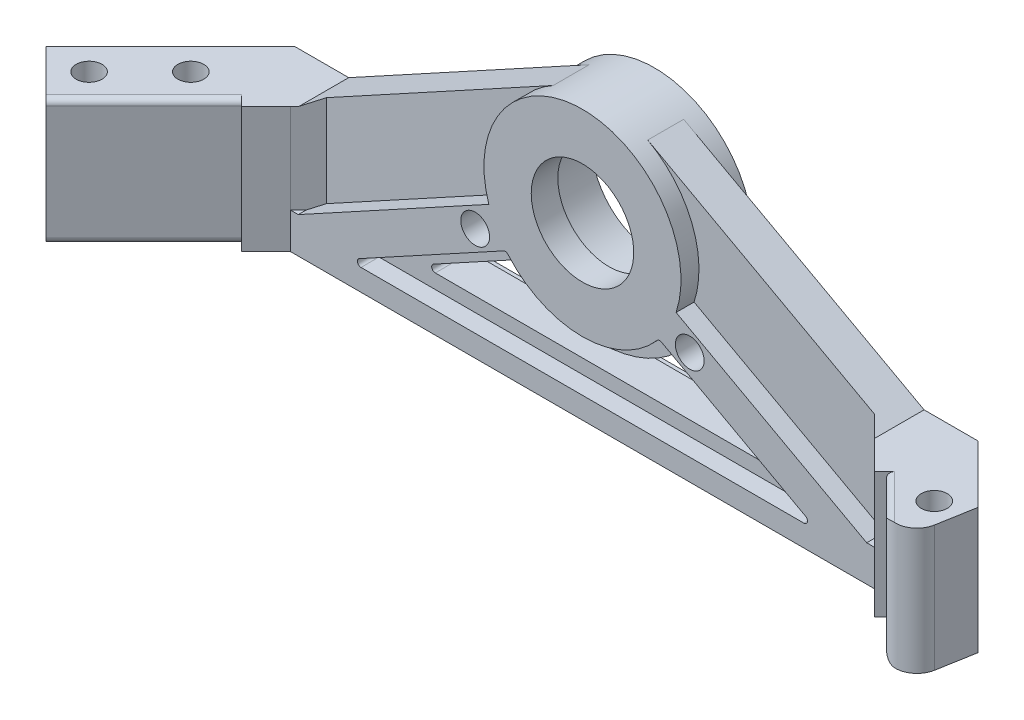
SolidWorks part; units mm, degrees
note: The reader was unsure of these and kept them because the rebuilt part matched: shared geometry of "Sketch2<3>", "Sketch2<5>", "Sketch5<3>".
ref_plane "Front Plane" through (0, 0, 0) normal (0, 0, 1) x (1, 0, 0)
ref_plane "Top Plane" through (0, 0, 0) normal (0, 1, 0) x (1, 0, 0)
ref_plane "Right Plane" through (0, 0, 0) normal (1, 0, 0) x (0, 0, -1)
sketch "Sketch1" plane through (0, 0, 0) normal (0, 1, 0) x (-1, 0, 0)
  line L48 (74.9309, 32.5085) -> (74.2125, 33.2269)
  line L49 (74.2125, 33.2269) -> (56.9345, 15.9489)
  line L50 (57.6529, 15.2305) -> (56.9345, 15.9489)
  line L51 (-56.9345, 15.9489) -> (-74.2125, 33.2269)
  line L52 (-74.2125, 33.2269) -> (-74.9309, 32.5085)
  line L53 (-56.9345, 15.9489) -> (-57.6529, 15.2305)
  line L54 (-65.0167, 7.8667) -> (-61.5144, 4.3644)
  line L55 (-61.5144, 4.3644) -> (-52.3715, 13.5073)
  line L56 (-52.3715, 13.5073) -> (-55.8738, 17.0096)
  line L57 (-55.8738, 17.0096) -> (-65.0167, 7.8667)
  line L58 (55.8738, 17.0096) -> (52.3715, 13.5073)
  line L59 (52.3715, 13.5073) -> (61.5144, 4.3644)
  line L60 (61.5144, 4.3644) -> (65.0167, 7.8667)
  line L61 (65.0167, 7.8667) -> (55.8738, 17.0096)
  line L62 (17.3112, 9.525) -> (13.6482, 9.525)
  line L63 (17.3112, 12.7) -> (-17.3112, 12.7)
  line L64 (-13.6482, 9.525) -> (-17.3112, 9.525)
  line L65 (-17.3112, 3.175) -> (-13.6482, 3.175)
  line L66 (-17.3112, 0) -> (17.3112, 0)
  line L67 (13.6482, 3.175) -> (17.3112, 3.175)
  line L68 (-17.3112, 12.7) -> (-53.1788, 12.7)
  line L69 (-53.1788, 12.7) -> (-50.0038, 9.525)
  line L70 (-50.0038, 9.525) -> (-17.3112, 9.525)
  line L71 (-60.325, 3.175) -> (-57.15, 0)
  line L72 (-57.15, 0) -> (-17.3112, 0)
  line L73 (-17.3112, 3.175) -> (-60.325, 3.175)
  line L74 (17.3112, 9.525) -> (50.0038, 9.525)
  line L75 (50.0038, 9.525) -> (53.1788, 12.7)
  line L76 (53.1788, 12.7) -> (17.3112, 12.7)
  line L77 (57.15, 0) -> (60.325, 3.175)
  line L78 (60.325, 3.175) -> (17.3112, 3.175)
  line L79 (17.3112, 0) -> (57.15, 0)
  line L80 (-74.9309, 32.5085) -> (-82.2947, 25.1447)
  line L81 (-82.2947, 25.1447) -> (-65.0167, 7.8667)
  line L82 (-65.0167, 7.8667) -> (-57.6529, 15.2305)
  line L83 (-60.325, 3.175) -> (-13.6482, 3.175)
  line L84 (-13.6482, 9.525) -> (-50.0038, 9.525)
  line L85 (-50.0038, 9.525) -> (-53.1788, 12.7)
  line L86 (-53.1788, 12.7) -> (-61.5144, 4.3644)
  line L87 (-61.5144, 4.3644) -> (-60.325, 3.175)
  line L88 (13.6482, 3.175) -> (60.325, 3.175)
  line L89 (60.325, 3.175) -> (61.5144, 4.3644)
  line L90 (61.5144, 4.3644) -> (53.1788, 12.7)
  line L91 (53.1788, 12.7) -> (50.0038, 9.525)
  line L92 (50.0038, 9.525) -> (13.6482, 9.525)
  line L93 (82.2947, 25.1447) -> (74.9309, 32.5085)
  line L94 (57.6529, 15.2305) -> (65.0167, 7.8667)
  line L95 (65.0167, 7.8667) -> (82.2947, 25.1447)
sketch "Sketch3" plane through (0, 0, 0) normal (0, 1, 0) x (1, 0, 0)
  line L0 (-53.1788, -12.7) -> (-17.3112, -12.7) construction
  line L1 (-17.3112, 0) -> (-57.15, 0) construction
  line L2 (-57.15, 0) -> (-60.325, -3.175) construction
  line L3 (-60.325, -3.175) -> (-61.5144, -4.3644) construction
  line L4 (-61.5144, -4.3644) -> (-65.0167, -7.8667) construction
  line L5 (-74.2125, -33.2269) -> (-56.9345, -15.9489) construction
  line L6 (-74.9309, -32.5085) -> (-74.2125, -33.2269) construction
  line L7 (-82.2947, -25.1447) -> (-74.9309, -32.5085) construction
  line L8 (-65.0167, -7.8667) -> (-82.2947, -25.1447) construction
  line L9 (-51.5642, -12.7) -> (-17.3112, -12.7)
  line L10 (-17.3112, 0) -> (-57.15, 0)
  line L11 (-57.15, 0) -> (-60.325, -3.175)
  line L12 (-60.325, -3.175) -> (-61.5144, -4.3644)
  line L13 (-61.5144, -4.3644) -> (-65.0167, -7.8667)
  line L14 (-74.2125, -33.2269) -> (-56.9345, -15.9489)
  line L15 (-74.9309, -32.5085) -> (-74.2125, -33.2269)
  line L16 (-82.2947, -25.1447) -> (-74.9309, -32.5085)
  line L17 (-65.0167, -7.8667) -> (-82.2947, -25.1447)
  line L18 (0, 0) -> (0, -12.7) construction
  line L19 (-17.3112, -12.7) -> (17.3112, -12.7) construction
  line L20 (17.3112, 0) -> (-17.3112, 0) construction
  line L21 (-52.3715, -13.5073) -> (-61.5144, -4.3644) construction
  line L22 (-65.0167, -7.8667) -> (-55.8738, -17.0096) construction
  line L23 (-55.8738, -17.0096) -> (-52.3715, -13.5073) construction
  line L24 (17.3112, 0) -> (-17.3112, 0)
  line L25 (-17.3112, -12.7) -> (17.3112, -12.7)
  line L26 (-52.3715, -13.5073) -> (-61.5144, -4.3644)
  line L27 (-65.0167, -7.8667) -> (-55.8738, -17.0096)
  line L28 (-55.8738, -17.0096) -> (-52.3715, -13.5073)
  line L29 (55.8738, -17.0096) -> (52.3715, -13.5073)
  line L30 (65.0167, -7.8667) -> (55.8738, -17.0096)
  line L31 (52.3715, -13.5073) -> (61.5144, -4.3644)
  line L32 (65.0167, -7.8667) -> (82.2947, -25.1447)
  line L33 (82.2947, -25.1447) -> (74.9309, -32.5085)
  line L34 (74.9309, -32.5085) -> (74.2125, -33.2269)
  line L35 (74.2125, -33.2269) -> (56.9345, -15.9489)
  line L36 (61.5144, -4.3644) -> (65.0167, -7.8667)
  line L37 (60.325, -3.175) -> (61.5144, -4.3644)
  line L38 (57.15, 0) -> (60.325, -3.175)
  line L39 (17.3112, 0) -> (57.15, 0)
  line L40 (51.5642, -12.7) -> (17.3112, -12.7)
  line L41 (-52.3715, -13.5073) -> (-51.5642, -12.7)
  line L42 (52.3715, -13.5073) -> (51.5642, -12.7)
extrude "Boss-Extrude1" add sketch "Sketch3" along normal mid plane 22.225 contours L27 L17 L16 L15 L14 | L27 L28 L26 L13 | L18 L24 L10 L11 L12 L26 L41 L9 L25 | L24 L18 L25 L40 L42 L31 L37 L38 L39 | L36 L31 L29 L30 | L35 L34 L33 L32 L30
sketch "Sketch2" plane through (0, 0, 0) normal (0, 0, 1) x (1, 0, 0)
  line L0 (0, 0) -> (0, 36.45) construction
  line L1 (-17.3112, 0) -> (17.3112, 0) construction
  line L2 (50.8048, 11.1125) -> (8.3447, 34.3184)
  line L3 (-50.8048, 11.1125) -> (-8.3447, 34.3184)
  line L4 (50.8048, 11.1125) -> (15.4841, 11.1125)
  line L5 (57.15, 11.1125) -> (-57.15, 11.1125) construction
  line L6 (-50.8048, 11.1125) -> (-15.4841, 11.1125)
  circle A0 centre (0, 19.05) radius 11.05
  circle A1 centre (0, 19.05) radius 17.4
  circle A2 centre (0, 19.05) radius 9.05
  dimension "D1" = 22.1
  dimension "D2" = 6.35
  dimension "D4" = 2
  dimension "D3" = 19.05
extrude "Boss-Extrude2" add sketch "Sketch2" along normal up to surface (12.7 mm away) contours A1 L3 L6 | A1 L0 A0 | A0 L0 | L0 A0 | L0 A1 A0 | A1 L4 L2 | A2
extrude "Cut-Extrude2" cut sketch "Sketch2<3>" along normal blind 8 contours A0 L0 A2 | A2 L0 | L0 A2 | L0 A0 A2
sketch "Sketch2<3>" plane through (0, 0, 0) normal (0, 0, 1) x (1, 0, 0) same geometry as "Sketch2"
extrude "Cut-Extrude3" cut sketch "Sketch2<5>" along normal through all contours A2 L0 | L0 A2
sketch "Sketch2<5>" plane through (0, 0, 0) normal (0, 0, 1) x (1, 0, 0) same geometry as "Sketch2"
sketch "Sketch5" plane through (0, 0, 0) normal (0, 0, -1) x (-1, 0, 0)
  line L0 (-16.5348, 13.6314) -> (-57.15, -8.5663)
  line L1 (-48.5682, -11.1125) -> (-13.4894, 8.0593)
  line L2 (0, 19.05) -> (-55.1885, -11.1125) construction
  line L3 (0, 19.05) -> (0, -11.1125) construction
  line L4 (16.5348, 13.6314) -> (57.15, -8.5663)
  line L5 (48.5682, -11.1125) -> (13.4894, 8.0593)
  line L6 (0, 19.05) -> (55.1885, -11.1125) construction
  line L7 (57.15, 11.1125) -> (50.8048, 11.1125)
  line L8 (50.8048, 11.1125) -> (8.3447, 34.3184)
  line L9 (-8.3447, 34.3184) -> (-50.8048, 11.1125)
  line L10 (-50.8048, 11.1125) -> (-57.15, 11.1125)
  line L11 (-57.15, 11.1125) -> (-57.15, -11.1125)
  line L12 (-57.15, -11.1125) -> (57.15, -11.1125)
  line L13 (57.15, -11.1125) -> (57.15, 11.1125)
  line L14 (57.15, 11.1125) -> (50.8048, 11.1125)
  line L15 (50.8048, 11.1125) -> (8.3447, 34.3184)
  line L16 (-8.3447, 34.3184) -> (-50.8048, 11.1125)
  line L17 (-50.8048, 11.1125) -> (-57.15, 11.1125)
  line L18 (-57.15, 11.1125) -> (-57.15, -11.1125)
  line L19 (-57.15, -11.1125) -> (57.15, -11.1125)
  line L20 (57.15, -11.1125) -> (57.15, 11.1125)
  line L21 (-41.597, -7.3025) -> (41.597, -7.3025)
  line L22 (-31.6533, -4.7625) -> (31.6533, -4.7625)
  line L23 (-31.6533, -4.7625) -> (-14.0224, 4.8734)
  line L24 (31.6533, -4.7625) -> (14.0224, 4.8734)
  line L25 (-57.15, 11.1125) -> (-82.2947, 11.1125)
  line L26 (-82.2947, 11.1125) -> (-82.2947, -11.1125)
  line L27 (-82.2947, -11.1125) -> (-57.15, -11.1125)
  line L28 (-82.2947, -4.7625) -> (-50.1902, -4.7625)
  line L29 (82.2947, -4.7625) -> (50.1902, -4.7625)
  line L33 (57.15, -11.1125) -> (82.2947, -11.1125)
  line L34 (82.2947, -11.1125) -> (82.2947, 11.1125)
  line L35 (82.2947, 11.1125) -> (57.15, 11.1125)
  line L36 (57.15, 11.1125) -> (57.15, -11.1125)
  line L37 (57.15, -11.1125) -> (82.2947, -11.1125)
  line L38 (82.2947, -11.1125) -> (82.2947, 11.1125)
  line L39 (82.2947, 11.1125) -> (57.15, 11.1125)
  line L40 (57.15, 11.1125) -> (57.15, -11.1125)
  circle A0 centre (0, 19.05) radius 11.05 construction
  arc A1 (8.3447, 34.3184) -> (-8.3447, 34.3184) centre (0, 19.05) ccw
  arc A2 (8.3447, 34.3184) -> (-8.3447, 34.3184) centre (0, 19.05) ccw
  circle A3 centre (0, 19.05) radius 11.05
  circle A4 centre (0, 19.05) radius 17.4
  arc A5 (-14.0224, 4.8734) -> (14.0224, 4.8734) centre (0, 19.05) ccw
  circle A6 centre (0, 19.05) radius 19.94 construction
  line M30 (57.15, 11.1125) -> (50.8048, 11.1125)
  line M31 (50.8048, 11.1125) -> (8.3447, 34.3184)
  line M33 (-8.3447, 34.3184) -> (-50.8048, 11.1125)
  line M34 (-50.8048, 11.1125) -> (-57.15, 11.1125)
  line M35 (-57.15, 11.1125) -> (-57.15, -11.1125)
  dimension "D2" = 3.175
  dimension "D3" = 3.175
  dimension "D4" = 3.81
  dimension "D6" = 2.54
  dimension "D7" = 2.54
  dimension "D9" = 6.35
  dimension "D1" = 0
  dimension "D5" = 2.54
  dimension "D8" = 0
extrude "Cut-Extrude4" cut sketch "Sketch5" against normal blind 3.175 contours L26 L28 L25 M35 | A4 L28 L0 M33 M34 M35 | A4 L4 L29 L20 M30 M31 | L38 L39 L20 L29 | A4 L1 L21 L5 L23 A5 L24 L22
extrude "Cut-Extrude5" cut sketch "Sketch5<3>" against normal through all contours A5 L23 L22 L24
sketch "Sketch5<3>" plane through (0, 0, 0) normal (0, 0, -1) x (-1, 0, 0) same geometry as "Sketch5"
sketch "Sketch6" plane through (0, 0, 0) normal (0, 0, -1) x (-1, 0, 0)
  line L0 (0, 19.05) -> (-18.9451, 8.6958) construction
  line L1 (-16.5348, 13.6314) -> (-50.1902, -4.7625) construction
  line L2 (0, 19.05) -> (0, 0) construction
  circle A0 centre (0, 19.05) radius 11.05 construction
  circle A1 centre (0, 19.05) radius 11.05 construction
  circle A2 centre (-18.9451, 8.6958) radius 2.54
  circle A3 centre (18.9451, 8.6958) radius 2.54
  dimension "D2" = 5.08
  dimension "D1" = 21.59
extrude "Cut-Extrude6" cut sketch "Sketch6" against normal through all contours A2 | A3
sketch "Sketch7" plane through (0, 0, 12.7) normal (0, 0, 1) x (1, 0, 0)
  line L0 (0, 19.05) -> (-51.5642, -9.1317) construction
  line L1 (0, 19.05) -> (0, 0) construction
  line L2 (0, 19.05) -> (51.5642, -9.1317) construction
  line L3 (-51.5642, -5.5134) -> (-8.9593, 17.7717)
  line L4 (-50.1902, -4.7625) -> (-51.5642, -4.7625)
  line L5 (-48.5189, -11.0856) -> (-5.9139, 12.1996)
  line L6 (48.5189, -11.0856) -> (5.9139, 12.1996)
  line L7 (51.5642, 11.1125) -> (50.8048, 11.1125)
  line L8 (50.8048, 11.1125) -> (8.3447, 34.3184)
  line L9 (-8.3447, 34.3184) -> (-50.8048, 11.1125)
  line L10 (-50.8048, 11.1125) -> (-51.5642, 11.1125)
  line L11 (-51.5642, 11.1125) -> (-51.5642, -11.1125)
  line L12 (-51.5642, -11.1125) -> (51.5642, -11.1125)
  line L13 (51.5642, -11.1125) -> (51.5642, 11.1125)
  line L14 (51.5642, 11.1125) -> (50.8048, 11.1125)
  line L15 (50.8048, 11.1125) -> (8.3447, 34.3184)
  line L16 (-8.3447, 34.3184) -> (-50.8048, 11.1125)
  line L17 (-50.8048, 11.1125) -> (-51.5642, 11.1125)
  line L18 (-51.5642, 11.1125) -> (-51.5642, -11.1125)
  line L19 (-51.5642, -11.1125) -> (51.5642, -11.1125)
  line L20 (51.5642, -11.1125) -> (51.5642, 11.1125)
  line L21 (50.1902, -4.7625) -> (51.5642, -4.7625)
  line L22 (51.5642, -5.5134) -> (8.9593, 17.7717)
  line L23 (-41.597, -7.3025) -> (41.597, -7.3025)
  circle A0 centre (0, 19.05) radius 9.05 construction
  arc A1 (8.3447, 34.3184) -> (-8.3447, 34.3184) centre (0, 19.05) ccw
  arc A2 (8.3447, 34.3184) -> (-8.3447, 34.3184) centre (0, 19.05) ccw
  circle A3 centre (0, 19.05) radius 9.05
  circle A4 centre (0, 19.05) radius 9.05
  circle A8 centre (0, 19.05) radius 17.4
  dimension "D2" = 6.35
  dimension "D3" = 6.35
  dimension "D4" = 3.81
  dimension "D1" = 0
extrude "Cut-Extrude7" cut sketch "Sketch7" against normal blind 3.175
chamfer "Chamfer1" distance 3.175 angle 45 3 edges at (51.5642, 3.175, 9.525) (-51.5642, 3.175, 9.525) (-50.8772, -4.7625, 9.525)
fillet "Fillet1" radius 0.635 12 edges at (-41.597, -7.3025, 1.5875) (41.597, -7.3025, 1.5875) (13.4894, 8.0593, 1.5875) (-13.4894, 8.0593, 1.5875) (14.0224, 4.8734, 6.35) (-14.0224, 4.8734, 6.35) (-31.6533, -4.7625, 6.35) (31.6533, -4.7625, 6.35) (41.597, -7.3025, 11.1125) (-41.597, -7.3025, 11.1125) (13.4894, 8.0593, 11.1125) (-13.4894, 8.0593, 11.1125)
fillet "Fillet3" radius 1.016 4 edges at (-65.5735, -11.1125, 24.5879) (-65.5735, 11.1125, 24.5879) (65.5735, -11.1125, 24.5879) (65.5735, 11.1125, 24.5879)
sketch "Sketch8" plane through (0, 11.1125, 0) normal (0, 1, 0) x (1, 0, 0)
  line L0 (57.6529, -15.2305) -> (55.8738, -17.0096) construction
  line L1 (57.6529, -15.2305) -> (55.8738, -17.0096)
  line L2 (0, 0) -> (0, -12.7) construction
  line L3 (17.4, 0) -> (-17.4, 0) construction
  line L4 (-17.4, -12.7) -> (17.4, -12.7) construction
  line L5 (57.6529, -15.2305) -> (65.0167, -7.8667)
  line L6 (60.325, -3.175) -> (82.2947, -25.1447) construction
  line L7 (61.1552, -11.7282) -> (78.4332, -29.0062) construction
  line L8 (82.2947, -25.1447) -> (74.9309, -32.5085) construction
  line L10 (-57.6529, -15.2305) -> (-55.8738, -17.0096)
  line L11 (-57.6529, -15.2305) -> (-65.0167, -7.8667)
  line L12 (-61.1552, -11.7282) -> (-78.4332, -29.0062) construction
  circle A0 centre (65.6453, -16.2183) radius 2.286
  circle A1 centre (74.6256, -25.1986) radius 2.286
  circle A2 centre (-65.6453, -16.2183) radius 2.286
  circle A3 centre (-74.6256, -25.1986) radius 2.286
  dimension "D2" = 4.572
  dimension "D3" = 4.572
  dimension "D1" = 5.461
  dimension "D4" = 6.35
  dimension "D5" = 12.7
extrude "Cut-Extrude8" cut sketch "Sketch8" against normal through all contours A1 | A3 | A0 | A2
sketch "Sketch9" plane through (0, 11.1125, 0) normal (0, 1, 0) x (1, 0, 0)
  line L0 (0, 0) -> (0, -12.7) construction
  line L1 (-17.4, -12.7) -> (17.4, -12.7) construction
  line L2 (70.485, -13.335) -> (65.6394, -40.8157)
  line L3 (60.325, -3.175) -> (82.2947, -25.1447) construction
  line L4 (65.6394, -40.8157) -> (98.2016, -40.8157)
  line L5 (98.2016, -40.8157) -> (98.2016, -13.335)
  line L6 (98.2016, -13.335) -> (70.485, -13.335)
  line L7 (-98.2016, -40.8157) -> (-98.2016, -13.335)
  line L8 (-65.6394, -40.8157) -> (-98.2016, -40.8157)
  line L9 (-70.485, -13.335) -> (-65.6394, -40.8157)
  line L10 (-98.2016, -13.335) -> (-70.485, -13.335)
  dimension "D1" = 13.335
  dimension "D2" = 100
extrude "Cut-Extrude9" cut sketch "Sketch9" against normal through all contours L6 L2 L4 L5
fillet "Fillet4" radius 3.81 1 edges at (68.062, 0, 27.0765)
sketch "Sketch10" plane through (0, -11.1125, 0) normal (0, -1, 0) x (1, 0, 0)
  line L0 (0, 0) -> (0, 12.7) construction
  line L1 (57.15, 0) -> (-57.15, 0) construction
  line L2 (-51.5642, 12.7) -> (51.5642, 12.7) construction
  line L3 (63.5, 6.35) -> (-63.5, 6.35) construction
  line L4 (-57.15, 0) -> (-82.2947, 25.1447) construction
  text T0 "<b>SN103</b>"
  point P11 (0, 6.35)
extrude "Cut-Extrude10" cut sketch "Sketch10" against normal blind 0.5
